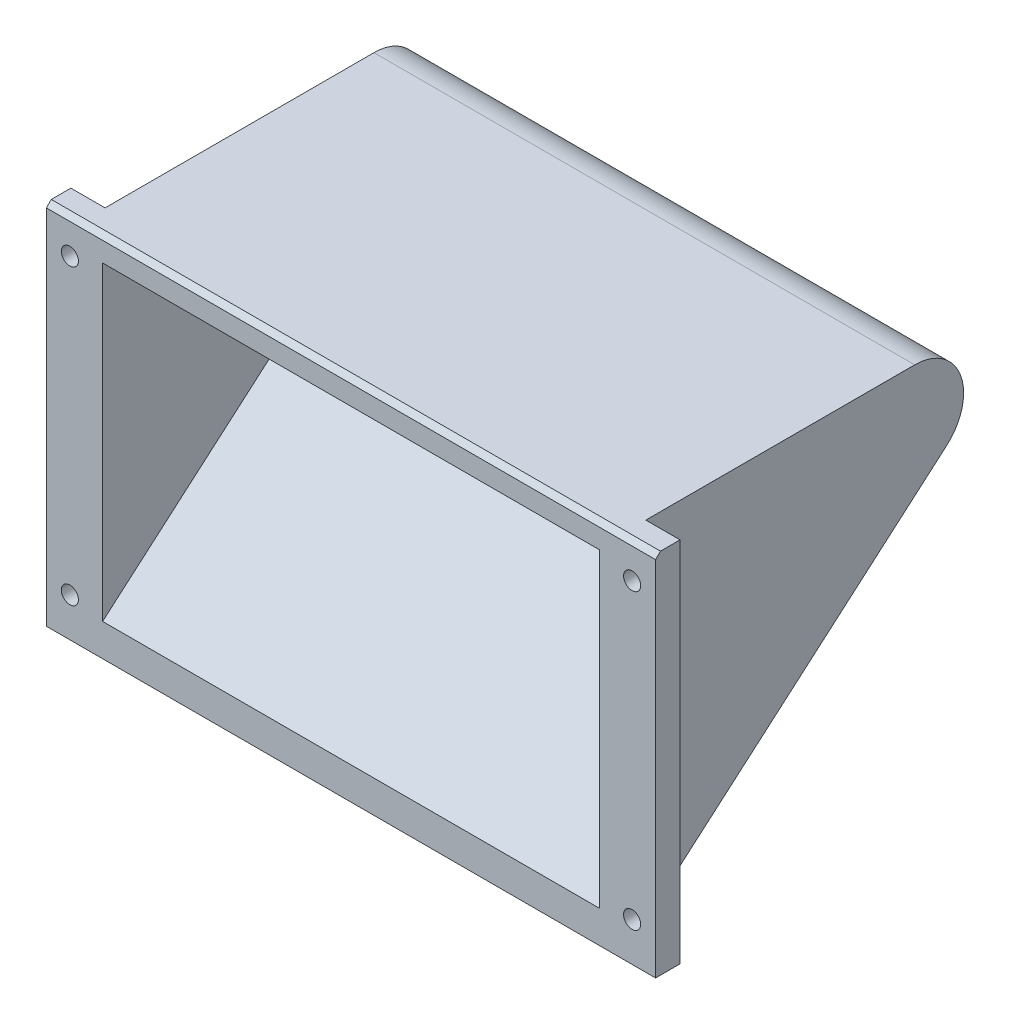
SolidWorks part; units mm, degrees
ref_plane "Front" through (0, 0, 0) normal (0, 0, 1) x (1, 0, 0)
ref_plane "Top" through (0, 0, 0) normal (0, 1, 0) x (1, 0, 0)
ref_plane "Right" through (0, 0, 0) normal (1, 0, 0) x (0, 0, -1)
sketch "Sketch1" plane through (0, 0, 0) normal (1, 0, 0) x (0, 0, -1)
  line L0 (0, 0) -> (60, 0)
  line L1 (63.2707, -8.7819) -> (0, -63.5)
  line L2 (0, 0) -> (0, 5)
  line L3 (0, 0) -> (0, -63.5) construction
  line L4 (0, 5) -> (60, 5)
  line L5 (66.5414, -12.5638) -> (0, -70.1105)
  line L6 (0, -70.1105) -> (0, -63.5)
  arc A0 (60, 0) -> (63.2707, -8.7819) centre (60, -5) cw
  arc A1 (60, 5) -> (66.5414, -12.5638) centre (60, -5) cw
  point P9 (73.4252, 0)
  dimension "D4" = 5
  dimension "D1" = 63.5
  dimension "D2" = 60
  dimension "D3" = 5
extrude "Boss-Extrude1" add sketch "Sketch1" along normal mid plane 101.6
sketch "Sketch3" plane through (50.8, 0, 0) normal (1, 0, 0) x (0, 0, -1)
  line L0 (0, 0) -> (0, -63.5)
  line L6 (0, 5) -> (0, 0)
  line L7 (0, 0) -> (60, 0)
  line L8 (63.2707, -8.7819) -> (0, -63.5)
  line L9 (0, -63.5) -> (0, -70.1105)
  line L10 (0, -70.1105) -> (66.5414, -12.5638)
  line L11 (60, 5) -> (0, 5)
  line L12 (0, 5) -> (0, 0)
  line L13 (0, 0) -> (60, 0)
  line L14 (63.2707, -8.7819) -> (0, -63.5)
  line L15 (0, -63.5) -> (0, -70.1105)
  line L16 (0, -70.1105) -> (66.5414, -12.5638)
  line L17 (60, 5) -> (0, 5)
  arc A2 (63.2707, -8.7819) -> (60, 0) centre (60, -5) ccw
  arc A3 (66.5414, -12.5638) -> (60, 5) centre (60, -5) ccw
  arc A4 (63.2707, -8.7819) -> (60, 0) centre (60, -5) ccw
  arc A5 (66.5414, -12.5638) -> (60, 5) centre (60, -5) ccw
  line M9 (0, 5) -> (0, 0)
  line M10 (0, 0) -> (60, 0)
  arc M11 (60, 0) -> (63.2707, -8.7819) centre (60, -5) cw
  line M12 (63.2707, -8.7819) -> (0, -63.5)
  line M13 (0, -63.5) -> (0, -70.1105)
  line M14 (0, -70.1105) -> (66.5414, -12.5638)
  arc M15 (66.5414, -12.5638) -> (60, 5) centre (60, -5) ccw
  line M16 (60, 5) -> (0, 5)
  dimension "D1" = 0
extrude "Boss-Extrude3" add sketch "Sketch3" along normal blind 4.5 contours M16 M9 M10 M11 M12 M13 M14 M15 | L0 M10 M12 M11 region at (50.8, -21.4686, -23.7908) region at (50.8, 2.5, -1.0267)
mirror "Mirror1" about plane through (0, 0, 0) normal (1, 0, 0) of "Boss-Extrude3"
sketch "Sketch4" plane through (0, 0, 0) normal (0, 0, 1) x (1, 0, 0)
  line L0 (-50.8, 5) -> (-50.8, -63.5)
  line L1 (55.3, 5) -> (-55.3, 5) construction
  line L2 (-50.8, -63.5) -> (50.8, -63.5)
  line L3 (50.8, -63.5) -> (50.8, 5)
  line L4 (50.8, 5) -> (62.3, 5)
  line L5 (62.3, 5) -> (62.3, -70.1105)
  line L6 (62.3, -70.1105) -> (-62.3, -70.1105)
  line L7 (-62.3, -70.1105) -> (-62.3, 5)
  line L8 (-62.3, 5) -> (-50.8, 5)
  line L9 (0, -63.5) -> (0, -70.1105) construction
  line L10 (55.3, 5) -> (55.3, -70.1105) construction
  line L11 (55.3, -70.1105) -> (-55.3, -70.1105) construction
  line M5 (-50.8, -63.5) -> (-50.8, 0)
  line M7 (50.8, 0) -> (50.8, -63.5)
  line M8 (50.8, -63.5) -> (-50.8, -63.5)
  line M9 (55.3, 5) -> (-55.3, 5)
  line M10 (-55.3, 5) -> (-55.3, -70.1105)
  line M11 (-55.3, -70.1105) -> (55.3, -70.1105)
  line M12 (55.3, -70.1105) -> (55.3, 5)
  dimension "D1" = 7
extrude "Boss-Extrude4" add sketch "Sketch4" against normal blind 5 contours L9 L2 L0 M5 M9 M10 M11 | L9 L8 L7 L6 M11 M10 | L9 L6 L5 L4 M11 M12 | L9 L3 M8 M11 M12 M9 M7 region at (-51.7327, 2.5, 0) region at (-58.8, -32.5552, 0) region at (53.05, 4.0673, 0) region at (58.8, -32.5552, 0)
sketch "Sketch6" plane through (0, 0, 0) normal (0, 0, 1) x (1, 0, 0)
  line L0 (62.3, 5) -> (-62.3, 5) construction
  line L1 (-57.5, -2.146) -> (57.5, -2.146) construction
  line L2 (-57.5, -2.146) -> (-57.5, -62.146) construction
  line L3 (-57.5, -62.146) -> (57.5, -62.146) construction
  line L4 (57.5, -2.146) -> (57.5, -62.146) construction
  line L5 (0, 0) -> (0, -2.146) construction
  circle A0 centre (-57.5, -2.146) radius 1.75
  circle A1 centre (-57.5, -62.146) radius 1.75
  circle A2 centre (57.5, -62.146) radius 1.75
  circle A3 centre (57.5, -2.146) radius 1.75
  dimension "D4" = 3.5
  dimension "D1" = 115
  dimension "D2" = 60
  dimension "D3" = 7.146
extrude "Cut-Extrude1" cut sketch "Sketch6" against normal blind 18.75
chamfer "Chamfer1" distance 1 angle 45 1 edges at (0, 5, 0)
